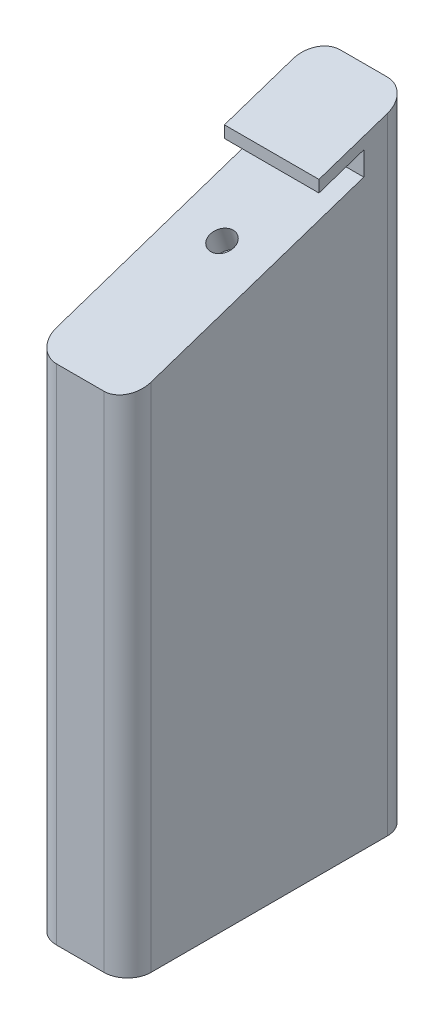
SolidWorks part; units mm, degrees
material "ABS"
ref_plane "Front Plane" through (0, 0, 0) normal (0, 0, 1) x (1, 0, 0)
ref_plane "Top Plane" through (0, 0, 0) normal (0, 1, 0) x (1, 0, 0)
ref_plane "Right Plane" through (0, 0, 0) normal (1, 0, 0) x (0, 0, -1)
sketch "Sketch1" plane through (0, 0, 0) normal (0, 1, 0) x (1, 0, 0)
  line L0 (-12.7, 25.4) -> (12.7, 25.4)
  line L1 (-12.7, -38.1) -> (12.7, -38.1)
  line L2 (-12.7, -38.1) -> (-12.7, 38.1)
  line L3 (-12.7, 38.1) -> (12.7, 38.1)
  line L4 (12.7, -38.1) -> (12.7, 38.1)
  line L5 (-12.7, -38.1) -> (12.7, 38.1) construction
  line L6 (-12.7, 38.1) -> (12.7, -38.1) construction
  point P0 (0, 0)
  dimension "D3" = 12.7
  dimension "D1" = 25.4
  dimension "D2" = 76.2
extrude "Boss-Extrude1" add sketch "Sketch1" along normal blind 160.782 contours L1 L4 L0 L2 | L0 L4 L3 L2 region at (0, 0, -31.75) region at (0, 0, 6.35)
sketch "Sketch4" plane through (12.7, 0, 0) normal (1, 0, 0) x (0, 0, -1)
  line L0 (38.1, 160.782) -> (-38.1, 160.782)
  line L1 (-38.1, 160.782) -> (-38.1, 135.2858)
  line L3 (-38.1, 135.2858) -> (38.1, 160.782)
  line L4 (-38.1, 135.2858) -> (38.1, 135.2858) construction
  line L7 (-38.1, 160.782) -> (-38.1, 0) construction
  line L8 (38.1, 160.782) -> (38.1, 0) construction
  dimension "D1" = 18.5
extrude "Cut-Extrude2" cut sketch "Sketch4" against normal through all both and the other way through all
sketch "Sketch5" plane through (0, 133.1295, 44.5445) normal (0, 0.9483, 0.3173) x (1, 0, 0)
  line L0 (0, 87.148) -> (0, 6.7957) construction
  line L1 (12.7, 87.148) -> (-12.7, 87.148) construction
  line L2 (-12.7, 6.7957) -> (12.7, 6.7957) construction
  line L3 (-12.7, 46.9719) -> (12.7, 46.9719) construction
  line L4 (-12.7, 6.7957) -> (-12.7, 87.148) construction
  line L5 (12.7, 87.148) -> (12.7, 6.7957) construction
  circle A0 centre (0, 46.9719) radius 3.175
  dimension "D1" = 6.35
extrude "Cut-Extrude3" cut sketch "Sketch5" against normal blind 6.35
ref_point "Point1"
extrude "Boss-Extrude2" add sketch "Sketch1<5>" along normal blind 9.525 from surface contours L0 L4 L3 L2 region at (0, 0, -31.75) starting at face at (0, 147.0265, 3.0109)
sketch "Sketch1<5>" plane through (0, 0, 0) normal (0, 1, 0) x (1, 0, 0) same geometry as "Sketch1"
sketch "Sketch8" plane through (0, 0, -25.4) normal (0, 0, 1) x (1, 0, 0)
  line L0 (12.7, 166.0576) -> (12.7, 156.5326) construction
  line L1 (-12.7, 166.0576) -> (12.7, 166.0576)
  line L2 (-12.7, 166.0576) -> (-12.7, 162.8826)
  line L3 (-12.7, 162.8826) -> (12.7, 162.8826)
  line L4 (12.7, 166.0576) -> (12.7, 162.8826)
  dimension "D1" = 3.175
extrude "Boss-Extrude3" add sketch "Sketch8" along direction (0, 0.3173, -0.9483) on the side of the normal blind 12.7
fillet "Fillet1" radius 6.35 4 edges at (-12.7, 85.1535, -38.1) (-12.7, 67.6429, 38.1) (12.7, 67.6429, 38.1)
